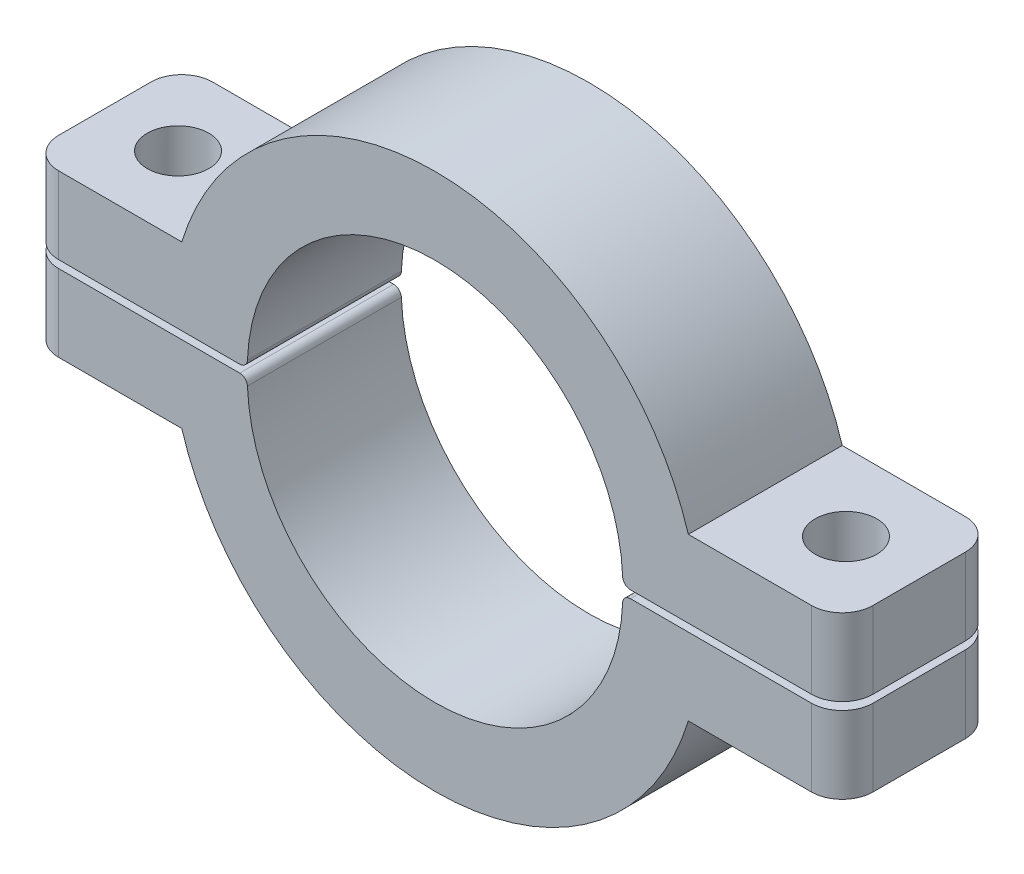
SolidWorks part; units mm, degrees
ref_plane "Front Plane" through (0, 0, 0) normal (0, 0, 1) x (1, 0, 0)
ref_plane "Top Plane" through (0, 0, 0) normal (0, 1, 0) x (1, 0, 0)
ref_plane "Right Plane" through (0, 0, 0) normal (1, 0, 0) x (0, 0, -1)
sketch "Sketch1" plane through (0, 0, 0) normal (0, 0, 1) x (1, 0, 0)
  line L0 (-26.4572, 0.25) -> (-12.2, 0.25)
  line L1 (12.2, 0.25) -> (26.4572, 0.25)
  line L2 (26.4572, 0.25) -> (26.4572, 5.25)
  line L3 (26.4572, 5.25) -> (16.4572, 5.25)
  line L4 (-16.4572, 5.25) -> (-26.4572, 5.25)
  line L5 (-26.4572, 5.25) -> (-26.4572, 0.25)
  line L6 (0, -55) -> (0, 55) construction
  arc A0 (-12.2, 0.25) -> (12.2, 0.25) centre (0, 0.25) cw
  arc A2 (-16.4572, 5.25) -> (16.4572, 5.25) centre (0, 0.25) cw
  dimension "D2" = 12.2
  dimension "D1" = 5
  dimension "D3" = 5
  dimension "D4" = 10
  dimension "D5" = 10
  dimension "D6" = 0.25
extrude "Boss-Extrude1" add sketch "Sketch1" along normal blind 10
fillet "Fillet1" radius 2 4 edges at (26.4572, 2.75, 0) (-26.4572, 2.75, 0) (26.4572, 2.75, 10) (-26.4572, 2.75, 10)
fillet "Fillet3" radius 0.5 2 edges at (-12.2, 0.25, 5) (12.2, 0.25, 5)
mirror "Mirror3" about plane through (0, 0, 0) normal (0, 1, 0) of bodies 101
sketch "Sketch3" plane through (0, 0, 0) normal (0, 1, 0) x (1, 0, 0)
  line L0 (-19.195, 0) -> (19.195, 0) construction
  line L1 (0, -5.5) -> (0, 5.5) construction
  circle A0 centre (-21.7, -5) radius 2
  circle A1 centre (21.7, -5) radius 2
  dimension "D3" = 5
  dimension "D1" = 4
  dimension "D2" = 4
  dimension "D4" = 5
  dimension "D5" = 21.7
  dimension "D6" = 21.7
extrude "Cut-Extrude1" cut sketch "Sketch3" against normal through all both and the other way through all
equation "\"shaftDiameter\"= 1in / 2"
equation "\"D2@Sketch1\"=\"shaftDiameter\"-0.5"
equation "\"D5@Sketch3\"=\"shaftDiameter\"+9"
equation "\"D6@Sketch3\"=\"D5@Sketch3\""
